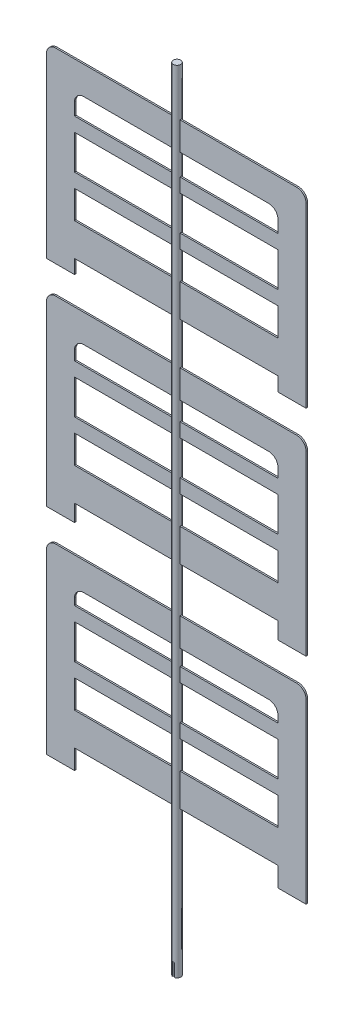
SolidWorks part; units mm, degrees
ref_plane "Ön Düzlem" through (0, 0, 0) normal (0, 0, 1) x (1, 0, 0)
ref_plane "Üst Düzlem" through (0, 0, 0) normal (0, 1, 0) x (1, 0, 0)
ref_plane "Sağ Düzlem" through (0, 0, 0) normal (1, 0, 0) x (0, 0, -1)
sketch "Çizim1" plane through (0, 0, 0) normal (0, 1, 0) x (1, 0, 0)
  circle A0 centre (0, 0) radius 20
  dimension "D1" = 40
extrude "Yükseklik-Ekstrüzyon1" add sketch "Çizim1" along normal mid plane 4177.4
sketch "Çizim2" plane through (0, -2088.7, 0) normal (0, -1, 0) x (1, 0, 0)
  line L1 (-6, 24) -> (6, 24)
  line L2 (-6, 24) -> (-6, 16)
  line L3 (-6, 16) -> (6, 16)
  line L4 (6, 24) -> (6, 16)
  line L5 (0, 16) -> (0, 24) construction
  line L6 (-6, 20) -> (6, 20) construction
  circle A0 centre (0, 0) radius 20 construction
  point P0 (0, 20)
  dimension "D1" = 8
  dimension "D2" = 12
extrude "Kes-Ekstrüzyon1" cut sketch "Çizim2" against normal blind 64.2
ref_plane "Düzlem1" through (0, 0, 19.08) normal (0, 0, 1) x (1, 0, 0)
sketch "Çizim3" plane through (0, 0, 19.08) normal (0, 0, 1) x (1, 0, 0)
  line L0 (6, -2024.5) -> (6, -2022.1)
  line L1 (-6, -2024.5) -> (-6, -2022.1)
  line L2 (6, -2024.5) -> (-6, -2024.5)
  arc A0 (6, -2022.1) -> (-6, -2022.1) centre (0, -2022.1) ccw
  dimension "D2" = 2.4
extrude "Kes-Ekstrüzyon4" cut sketch "Çizim3" against normal blind 3.08 and the other way blind 3.08
sketch "Çizim4" plane through (0, 0, 0) normal (0, 0, 1) x (1, 0, 0)
  line L7 (20, 1888.7) -> (645, 1888.7)
  line L8 (20, -2088.7) -> (20, 2088.7) construction
  line L9 (695, 1838.7) -> (695, 888.7)
  line L10 (695, 888.7) -> (545, 888.7)
  line L11 (545, 888.7) -> (545, 1688.7)
  line L12 (495, 1738.7) -> (20, 1738.7)
  line L13 (20, 1738.7) -> (20, 1888.7)
  line L14 (0, 0) -> (0, 3588.8123) construction
  line L15 (-495, 1738.7) -> (-20, 1738.7)
  line L16 (-545, 888.7) -> (-545, 1688.7)
  line L17 (-695, 888.7) -> (-545, 888.7)
  line L18 (-695, 1838.7) -> (-695, 888.7)
  line L19 (-20, 1888.7) -> (-645, 1888.7)
  line L20 (-20, 1738.7) -> (-20, 1888.7)
  line L21 (20, 588.7) -> (20, 738.7)
  line L22 (20, 738.7) -> (645, 738.7)
  line L23 (695, 688.7) -> (695, -261.3)
  line L24 (695, -261.3) -> (545, -261.3)
  line L25 (545, -261.3) -> (545, 538.7)
  line L26 (495, 588.7) -> (20, 588.7)
  line L27 (-495, 588.7) -> (-20, 588.7)
  line L28 (-20, 588.7) -> (-20, 738.7)
  line L29 (-20, 738.7) -> (-645, 738.7)
  line L30 (-695, 688.7) -> (-695, -261.3)
  line L31 (-695, -261.3) -> (-545, -261.3)
  line L32 (-545, -261.3) -> (-545, 538.7)
  line L33 (20, -561.3) -> (20, -411.3)
  line L34 (20, -411.3) -> (645, -411.3)
  line L35 (695, -461.3) -> (695, -1411.3)
  line L36 (695, -1411.3) -> (545, -1411.3)
  line L37 (545, -1411.3) -> (545, -611.3)
  line L38 (495, -561.3) -> (20, -561.3)
  line L39 (-495, -561.3) -> (-20, -561.3)
  line L40 (-20, -561.3) -> (-20, -411.3)
  line L41 (-20, -411.3) -> (-645, -411.3)
  line L42 (-695, -461.3) -> (-695, -1411.3)
  line L43 (-695, -1411.3) -> (-545, -1411.3)
  line L44 (-545, -1411.3) -> (-545, -611.3)
  arc A0 (-645, -411.3) -> (-695, -461.3) centre (-645, -461.3) ccw
  arc A1 (-495, -561.3) -> (-545, -611.3) centre (-495, -611.3) ccw
  arc A2 (545, -611.3) -> (495, -561.3) centre (495, -611.3) ccw
  arc A3 (645, -411.3) -> (695, -461.3) centre (645, -461.3) cw
  arc A4 (-695, 1838.7) -> (-645, 1888.7) centre (-645, 1838.7) cw
  arc A5 (-495, 1738.7) -> (-545, 1688.7) centre (-495, 1688.7) ccw
  arc A6 (545, 1688.7) -> (495, 1738.7) centre (495, 1688.7) ccw
  arc A7 (645, 1888.7) -> (695, 1838.7) centre (645, 1838.7) cw
  arc A8 (545, 538.7) -> (495, 588.7) centre (495, 538.7) ccw
  arc A9 (-495, 588.7) -> (-545, 538.7) centre (-495, 538.7) ccw
  arc A10 (-645, 738.7) -> (-695, 688.7) centre (-645, 688.7) ccw
  arc A11 (645, 738.7) -> (695, 688.7) centre (645, 688.7) cw
  point P52 (-695, 1888.7)
  point P55 (-545, 1738.7)
  point P58 (545, 1738.7)
  point P61 (695, 1888.7)
  dimension "D8" = 50
  dimension "D1" = 200
  dimension "D2" = 150
  dimension "D3" = 150
  dimension "D4" = 1000
  dimension "D5" = 675
  dimension "D7" = 150
  dimension "D6" = 3
extrude "Yükseklik-Ekstrüzyon2" add sketch "Çizim4" along normal mid plane 8 separate body
sketch "Çizim5" plane through (0, 0, -4) normal (0, 0, -1) x (-1, 0, 0)
  line L0 (-20, -561.3) -> (20, -561.3)
  line L1 (20, -561.3) -> (20, -411.3)
  line L2 (20, -411.3) -> (-20, -411.3)
  line L3 (-20, -411.3) -> (-20, -561.3)
  line L4 (-20, 738.7) -> (-20, 588.7)
  line L5 (-20, 588.7) -> (20, 588.7)
  line L6 (20, 588.7) -> (20, 738.7)
  line L7 (20, 738.7) -> (-20, 738.7)
  line L8 (-20, 1888.7) -> (-20, 1738.7)
  line L9 (-20, 1738.7) -> (20, 1738.7)
  line L10 (20, 1738.7) -> (20, 1888.7)
  line L11 (20, 1888.7) -> (-20, 1888.7)
  dimension "D2" = 1000
  dimension "D1" = 3
extrude "Yükseklik-Ekstrüzyon3" add sketch "Çizim5" against normal blind 8
sketch "Çizim6" plane through (0, 0, -4) normal (0, 0, -1) x (-1, 0, 0)
  line L0 (-545, 538.7) -> (-545, -261.3) construction
  line L1 (545, 413.7) -> (-545, 413.7)
  line L2 (545, 413.7) -> (545, 488.7)
  line L3 (545, 488.7) -> (-545, 488.7)
  line L4 (-545, 413.7) -> (-545, 488.7)
  line L5 (0, 488.7) -> (0, 413.7) construction
  line L6 (545, 451.2) -> (-545, 451.2) construction
  line L8 (545, 153.7) -> (-545, 153.7)
  line L9 (545, 153.7) -> (545, 228.7)
  line L10 (545, 228.7) -> (-545, 228.7)
  line L11 (-545, 153.7) -> (-545, 228.7)
  line L12 (0, 228.7) -> (0, 153.7) construction
  line L13 (545, 191.2) -> (-545, 191.2) construction
  line L14 (545, 3.7) -> (-545, 3.7)
  line L15 (545, 3.7) -> (545, -171.3)
  line L16 (545, -171.3) -> (-545, -171.3)
  line L17 (-545, 3.7) -> (-545, -171.3)
  line L18 (0, -171.3) -> (0, 3.7) construction
  line L19 (545, -83.8) -> (-545, -83.8) construction
  line L20 (545, 1138.7) -> (545, 963.7)
  line L21 (545, 1138.7) -> (-545, 1138.7)
  line L22 (-545, 1138.7) -> (-545, 963.7)
  line L23 (545, 963.7) -> (-545, 963.7)
  line L24 (545, 1288.7) -> (545, 1363.7)
  line L25 (545, 1288.7) -> (-545, 1288.7)
  line L26 (-545, 1288.7) -> (-545, 1363.7)
  line L27 (545, 1363.7) -> (-545, 1363.7)
  line L28 (545, 1548.7) -> (545, 1623.7)
  line L29 (545, 1548.7) -> (-545, 1548.7)
  line L30 (-545, 1548.7) -> (-545, 1623.7)
  line L31 (545, 1623.7) -> (-545, 1623.7)
  line L32 (545, -1131.3) -> (545, -1306.3)
  line L33 (545, -1131.3) -> (-545, -1131.3)
  line L34 (-545, -1131.3) -> (-545, -1306.3)
  line L35 (545, -1306.3) -> (-545, -1306.3)
  line L36 (545, -981.3) -> (545, -906.3)
  line L37 (545, -981.3) -> (-545, -981.3)
  line L38 (-545, -981.3) -> (-545, -906.3)
  line L39 (545, -906.3) -> (-545, -906.3)
  line L40 (545, -721.3) -> (545, -646.3)
  line L41 (545, -721.3) -> (-545, -721.3)
  line L42 (-545, -721.3) -> (-545, -646.3)
  line L43 (545, -646.3) -> (-545, -646.3)
  line L44 (545, 888.7) -> (545, 1688.7) construction
  line L46 (545, -261.3) -> (545, 538.7) construction
  point P0 (0, 451.2)
  point P6 (0, 191.2)
  point P10 (0, -83.8)
  dimension "D1" = 175
  dimension "D2" = 75
  dimension "D3" = 75
  dimension "D4" = 150
  dimension "D5" = 185
  dimension "D8" = 475
  dimension "D9" = 475
  dimension "D10" = 90
  dimension "D6" = 2
  dimension "D7" = 2
extrude "Yükseklik-Ekstrüzyon4" add sketch "Çizim6" against normal blind 8
sketch "Çizim7" plane through (0, 2088.7, 0) normal (0, 1, 0) x (1, 0, 0)
  circle A0 centre (0, 0) radius 20
extrude "Yükseklik-Ekstrüzyon5" add sketch "Çizim7" along normal blind 55
